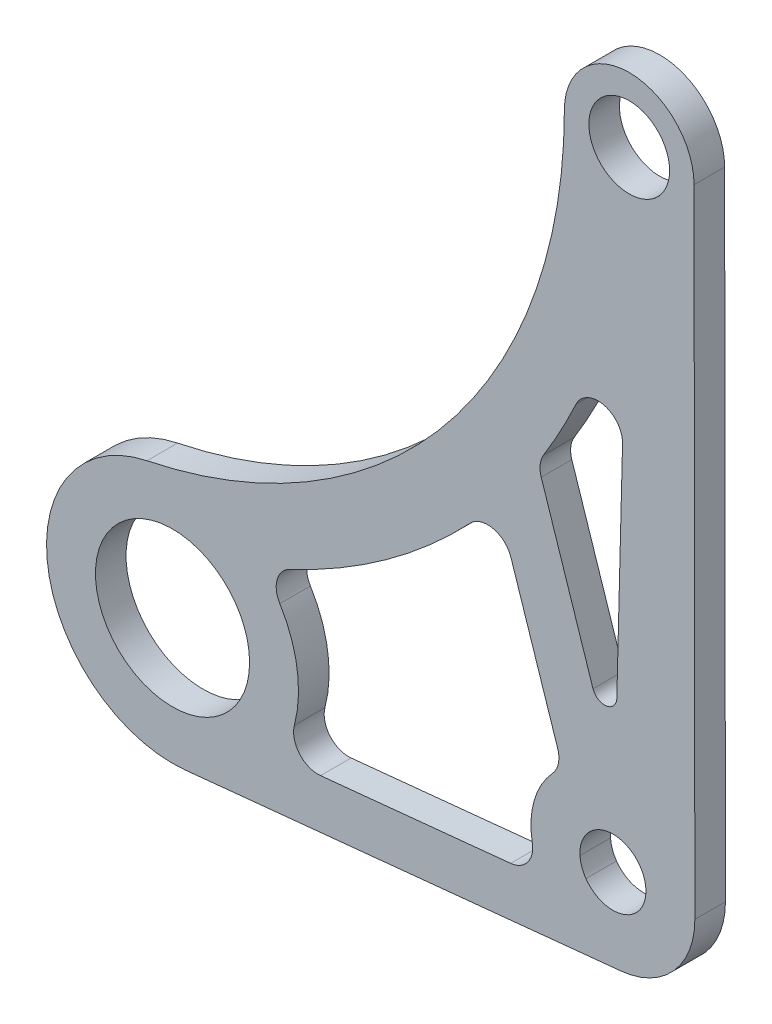
SolidWorks part; units mm, degrees
material "6061-T6 (SS)"
ref_plane "Front Plane" through (0, 0, 0) normal (0, 0, 1) x (1, 0, 0)
ref_plane "Top Plane" through (0, 0, 0) normal (0, 1, 0) x (1, 0, 0)
ref_plane "Right Plane" through (0, 0, 0) normal (1, 0, 0) x (0, 0, -1)
sketch "Sketch2" plane through (0, 0, 0) normal (0, 0, 1) x (1, 0, 0)
  line L0 (0, 0) -> (45.72, 0) construction
  line L1 (45.72, 0) -> (47.4133, 66.0183) construction
  line L2 (47.4133, 66.0183) -> (0, 0) construction
  line L3 (-9.9962, 8.4373) -> (42.2697, 70.3598)
  line L4 (54.1443, 66.0269) -> (54.229, 0.0109)
  line L5 (46.5709, -8.4663) -> (1.3081, -13.0154)
  line L6 (-6.2728, 4.9667) -> (44.1276, 68.6199)
  line L7 (0.8001, -7.9609) -> (46.0629, -3.4118)
  line L8 (49.1466, -0.1275) -> (51.6014, 65.8625)
  line L9 (40.6823, 66.0183) -> (40.6823, 38.0486)
  line L10 (45.72, 0) -> (38.8832, 9.7026) construction
  line L11 (45.72, 0) -> (42.0108, 11.275) construction
  line L12 (45.72, 0) -> (44.9726, 11.8459) construction
  line L13 (47.2407, 59.2895) -> (45.9382, 8.5062)
  line L14 (45.72, 0) -> (35.8675, 29.9488) construction
  line L15 (33.7519, 27.2103) -> (40.4943, 6.7153)
  line L16 (37.9047, 32.9259) -> (45.9382, 8.5062)
  line L17 (40.7938, 14.9744) -> (38.0718, 14.0789) construction
  line L18 (40.7938, 14.9744) -> (43.5157, 15.8698) construction
  circle A0 centre (0, 0) radius 8.001
  circle A1 centre (45.72, 0) radius 3.429
  circle A2 centre (47.4133, 66.0183) radius 4.191
  circle A3 centre (0, 0) radius 13.081
  circle A4 centre (45.72, 0) radius 8.509
  circle A5 centre (47.4133, 66.0183) radius 6.731
  circle A6 centre (-13.6517, 66.0183) radius 54.334
  circle A7 centre (-13.6517, 66.0183) radius 61.2631
  point P29 (47.2407, 59.2895)
  point P30 (45.72, 0)
  dimension "D1" = 8.382
  dimension "D2" = 6.858
  dimension "D3" = 16.002
  dimension "2.7" = 45.72
  dimension "D5" = 66.04
  dimension "D6" = 5.08
  dimension "D7" = 2.54
  dimension "D8" = 5.08
  dimension "D9" = 81.28
  dimension "D4" = 54.83
  dimension "D10" = 71.79
  dimension "D11" = 86.39
extrude "Boss-Extrude1" add sketch "Sketch2" along normal blind 3.175 contours A2 A7 A5 L6 | A7 A2 L8 A5 | A7 A5 L8 A2 | A5 A7 A2 L6 | A5 L9 L6 | A6 L6 L9 | A3 A7 A5 L6 A6 | A5 L8 A4 L4 | A5 L13 A4 L8 | A4 L8 A1 L7 | L8 A4 L7 A1 | A4 L7 A3 L5 | A7 A3 L7 A0 L6 | A7 A0 L7 A3 | L6 A7 A0 A3 | A3 A7 L6 | A7 L15 A4 L16 | A6 A3 L6 | A7 L6 A0 region at (-6.3075, 8.69, 0) region at (-0.4084, 13.2081, 0) region at (-9.095, 4.6208, 0) region at (2.3492, 9.8578, 0) region at (29.465, 32.4244, 0) region at (24.4662, -8.3164, 0) region at (43.762, 69.4754, 0) region at (51.4426, 67.8166, 0) region at (-6.1151, 5.1624, 0) region at (40.736, 64.7898, 0) region at (40.6735, 64.6922, 0) region at (9.2429, 0.5284, 0) region at (48.4339, -2.5482, 0) region at (43.9455, 62.5512, 0) region at (39.5545, 19.0131, 0) region at (42.6926, 2.8425, 0) region at (52.3142, 31.1167, 0) region at (48.5371, 34.6164, 0) region at (49.5884, 61.2911, 0)
ref_plane "Plane2" through (45.72, 0, 0) normal (-0.576, 0.8174, 0) x (0.8174, 0.576, 0)
split line "Split Line2"
ref_plane "Plane3" through (45.72, 0, 0) normal (-0.063, 0.998, 0) x (0.998, 0.063, 0)
split line "Split Line3"
fillet "Fillet1" radius 2.54 4 edges at (9.2873, 9.2119, 1.5875) (11.097, -6.926, 1.5875) (38.3144, -4.1906, 1.5875) (47.2407, 59.2895, 1.5875)
fillet "Fillet2" radius 2.54 3 edges at (40.4943, 6.7153, 1.5875) (37.9047, 32.9259, 1.5875) (33.7519, 27.2103, 1.5875)
fillet "Fillet3" radius 1.27 1 edges at (45.9382, 8.5062, 1.5875)
equation "\"Droop angle\"= 54.83"
equation "\"Static angle\"= 71.79"
equation "\"Jounce angle\"= 86.39"
equation "\"D4@Sketch2\"=\"Droop angle\""
equation "\"D10@Sketch2\"=\"Static angle\""
equation "\"D11@Sketch2\"=\"Jounce angle\""
